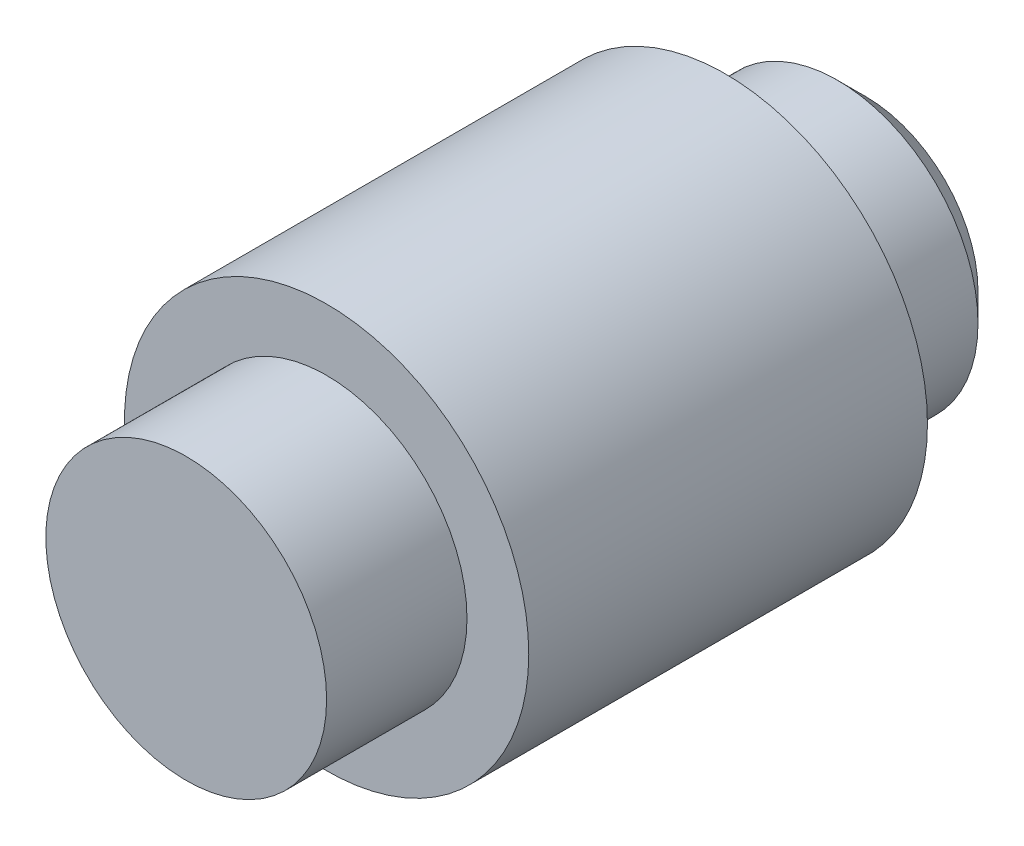
SolidWorks part; units mm, degrees
ref_plane "Front Plane" through (0, 0, 0) normal (0, 0, 1) x (1, 0, 0)
ref_plane "Top Plane" through (0, 0, 0) normal (0, 1, 0) x (1, 0, 0)
ref_plane "Right Plane" through (0, 0, 0) normal (1, 0, 0) x (0, 0, -1)
sketch "Sketch2" plane through (0, 0, 0) normal (0, 0, 1) x (1, 0, 0)
  circle A0 centre (0, 0) radius 1.25
  dimension "D1" = 2.5
sketch "Sketch3" plane through (0, 0, 0) normal (0, 0, 1) x (1, 0, 0)
  line L5 (-3.6, 3.6) -> (3.6, 3.6) construction
  line L6 (-3.6, 3.6) -> (-3.6, -3.6) construction
  line L7 (-3.6, -3.6) -> (3.6, -3.6) construction
  line L8 (3.6, 3.6) -> (3.6, -3.6) construction
  circle A0 centre (0, 0) radius 3.6
  point P4 (0, 3.6)
  point P6 (-3.6, 0)
  dimension "D1" = 7.2
extrude "Boss-Extrude1" add sketch "Sketch3" along normal blind 7.1
sketch "Sketch4" plane through (0, 0, 0) normal (0, 0, 1) x (1, 0, 0)
  circle A0 centre (0, 0) radius 2.5
  dimension "D1" = 5
extrude "Boss-Extrude2" add sketch "Sketch4" against normal blind 2.5
sketch "Sketch5" plane through (0, 0, 7.1) normal (0, 0, 1) x (1, 0, 0)
  circle A0 centre (0, 0) radius 2.5
  dimension "D1" = 5
extrude "Boss-Extrude3" add sketch "Sketch5" along normal blind 2.5
chamfer "Chamfer1" distance 0.5 angle 45 1 edges at (2.5, 0, -2.5)
equation "\"length\"=7.1"
equation "\"D1@Boss-Extrude1\"=\"length\""
equation "\"hole\"=5"
equation "\"D1@Sketch5\"=\"hole\""
equation "\"D1@Sketch4\"=\"hole\""
